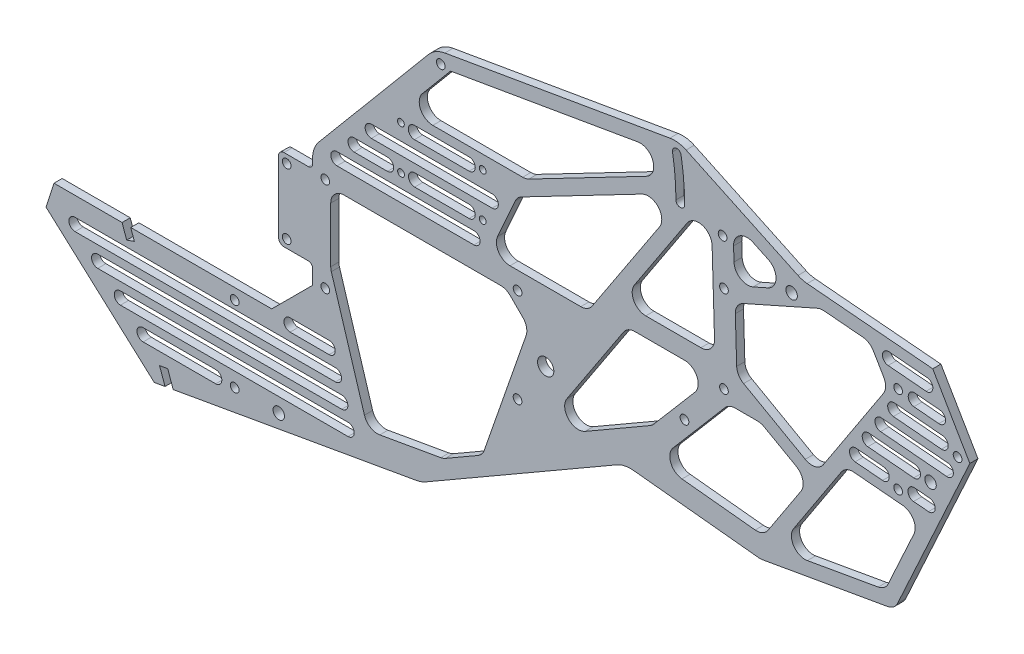
SolidWorks part; units mm, degrees
ref_plane "Front Plane" through (0, 0, 0) normal (0, 0, 1) x (1, 0, 0)
ref_plane "Top Plane" through (0, 0, 0) normal (0, 1, 0) x (1, 0, 0)
ref_plane "Right Plane" through (0, 0, 0) normal (1, 0, 0) x (0, 0, -1)
sketch "Sketch1" plane through (0, 0, 0) normal (0, 0, 1) x (1, 0, 0)
  line L0 (-2, -20.1357) -> (-28.6473, -20.1357) construction
  line L1 (-28.6473, -15.5958) -> (-2, -15.5958) construction
  line L2 (46.6267, -12.6057) -> (-36.9862, -12.6057) construction
  line L3 (-36.9862, -8.0658) -> (46.6267, -8.0658) construction
  line L4 (44.3092, -5.0757) -> (-45.3251, -5.0757) construction
  line L5 (-45.3251, -0.5358) -> (44.3092, -0.5358) construction
  line L6 (41.9917, 2.4543) -> (-53.664, 2.4543) construction
  line L7 (-53.664, 6.9942) -> (41.9917, 6.9942) construction
  line L8 (39.6742, 9.9843) -> (25.3518, 9.9843) construction
  line L9 (25.3518, 14.5242) -> (39.6742, 14.5242) construction
  line L10 (-2, -20.1357) -> (-28.6473, -20.1357)
  line L11 (-28.6473, -15.5958) -> (-2, -15.5958)
  line L12 (46.6267, -12.6057) -> (-36.9862, -12.6057)
  line L13 (-36.9862, -8.0658) -> (46.6267, -8.0658)
  line L14 (44.3092, -5.0757) -> (-45.3251, -5.0757)
  line L15 (-45.3251, -0.5358) -> (44.3092, -0.5358)
  line L16 (41.9917, 2.4543) -> (-53.664, 2.4543)
  line L17 (-53.664, 6.9942) -> (41.9917, 6.9942)
  line L18 (39.6742, 9.9843) -> (25.3518, 9.9843)
  line L19 (25.3518, 14.5242) -> (39.6742, 14.5242)
  line L20 (80.7464, -2.2866) -> (58.3209, -6.2408) construction
  line L21 (106.2441, 62.0298) -> (110.8759, 57.3979) construction
  line L22 (45.2764, 63.4942) -> (102.7085, 63.4942) construction
  line L23 (40.2764, 38.2462) -> (40.2764, 58.4942) construction
  line L24 (52.6739, -2.7875) -> (40.4976, 36.7755) construction
  line L25 (112.0626, 52.2191) -> (96.66, 7.9568) construction
  line L26 (33.6064, 69.3545) -> (33.6064, 67.4942)
  line L27 (76.2479, 123.8124) -> (35.946, 75.7824)
  line L28 (164.9022, 141.4902) -> (82.21, 127.2392)
  line L29 (211.9524, 121.3273) -> (170.8618, 140.6821)
  line L30 (261.4848, 116.375) -> (215.3421, 120.412)
  line L31 (275.1174, 93.0694) -> (261.4848, 116.375)
  line L32 (266.371, 74.0309) -> (275.1174, 93.0694)
  line L33 (151.4467, 29.0597) -> (212.4327, 22.7334)
  line L34 (75.0971, -12.8246) -> (145.4149, 27.7734)
  line L35 (-17.6047, -29.7828) -> (71.8336, -14.0124)
  line L36 (-19.6192, -24.1311) -> (-17.6047, -29.7828)
  line L37 (-22.6157, -24.6595) -> (-19.6192, -24.1311)
  line L38 (-20.6012, -30.3112) -> (-22.6157, -24.6595)
  line L39 (-24.5404, -31.0058) -> (-20.6012, -30.3112)
  line L40 (-64.3382, 4.9315) -> (-24.5404, -31.0058)
  line L41 (-61.3936, 13.9942) -> (-64.3382, 4.9315)
  line L42 (-36.3936, 13.9942) -> (-61.3936, 13.9942)
  line L43 (-34.6915, 9.2192) -> (-36.3936, 13.9942)
  line L44 (-31.8657, 10.2264) -> (-34.6915, 9.2192)
  line L45 (-33.2087, 13.9942) -> (-31.8657, 10.2264)
  line L46 (18.6064, 13.9942) -> (-33.2087, 13.9942)
  line L47 (33.6064, 28.9942) -> (18.6064, 13.9942)
  line L48 (33.6064, 34.4942) -> (33.6064, 28.9942)
  line L49 (23.1064, 35.9942) -> (32.1064, 35.9942)
  line L50 (21.1064, 63.9942) -> (21.1064, 37.9942)
  line L51 (32.1064, 65.9942) -> (23.1064, 65.9942)
  line L52 (33.6064, 69.3545) -> (33.6064, 67.4942)
  line L53 (76.2479, 123.8124) -> (35.946, 75.7824)
  line L54 (164.9022, 141.4902) -> (82.21, 127.2392)
  line L55 (211.9524, 121.3273) -> (170.8618, 140.6821)
  line L56 (261.4848, 116.375) -> (215.3421, 120.412)
  line L57 (275.1174, 93.0694) -> (261.4848, 116.375)
  line L58 (266.371, 74.0309) -> (275.1174, 93.0694)
  line L59 (151.4467, 29.0597) -> (212.4327, 22.7334)
  line L60 (75.0971, -12.8246) -> (145.4149, 27.7734)
  line L61 (-17.6047, -29.7828) -> (71.8336, -14.0124)
  line L62 (-19.6192, -24.1311) -> (-17.6047, -29.7828)
  line L63 (-22.6157, -24.6595) -> (-19.6192, -24.1311)
  line L64 (-20.6012, -30.3112) -> (-22.6157, -24.6595)
  line L65 (-24.5404, -31.0058) -> (-20.6012, -30.3112)
  line L66 (-64.3382, 4.9315) -> (-24.5404, -31.0058)
  line L67 (-61.3936, 13.9942) -> (-64.3382, 4.9315)
  line L68 (-36.3936, 13.9942) -> (-61.3936, 13.9942)
  line L69 (-34.6915, 9.2192) -> (-36.3936, 13.9942)
  line L70 (-31.8657, 10.2264) -> (-34.6915, 9.2192)
  line L71 (-33.2087, 13.9942) -> (-31.8657, 10.2264)
  line L72 (18.6064, 13.9942) -> (-33.2087, 13.9942)
  line L73 (33.6064, 28.9942) -> (18.6064, 13.9942)
  line L74 (33.6064, 34.4942) -> (33.6064, 28.9942)
  line L75 (23.1064, 35.9942) -> (32.1064, 35.9942)
  line L76 (21.1064, 63.9942) -> (21.1064, 37.9942)
  line L77 (32.1064, 65.9942) -> (23.1064, 65.9942)
  line L78 (94.4378, 5.2699) -> (82.3782, -1.6927) construction
  line L79 (112.0626, 52.2191) -> (96.66, 7.9568)
  line L80 (94.4378, 5.2699) -> (82.3782, -1.6927)
  line L81 (80.7464, -2.2866) -> (58.3209, -6.2408)
  line L82 (52.6739, -2.7875) -> (40.4976, 36.7755)
  line L83 (40.2764, 38.2462) -> (40.2764, 58.4942)
  line L84 (45.2764, 63.4942) -> (102.7085, 63.4942)
  line L85 (106.2441, 62.0298) -> (110.8759, 57.3979)
  arc A0 (46.6267, -12.6057) -> (46.6267, -8.0658) centre (46.6267, -10.3357) ccw construction
  arc A1 (44.3092, -5.0757) -> (44.3092, -0.5358) centre (44.3092, -2.8057) ccw construction
  circle A2 centre (5, -17.8657) radius 1.6 construction
  arc A3 (-2, -20.1357) -> (-2, -15.5958) centre (-2, -17.8657) ccw construction
  arc A4 (-28.6473, -15.5958) -> (-28.6473, -20.1357) centre (-28.6473, -17.8657) ccw construction
  arc A5 (-36.9862, -8.0658) -> (-36.9862, -12.6057) centre (-36.9862, -10.3357) ccw construction
  arc A6 (-45.3251, -0.5358) -> (-45.3251, -5.0757) centre (-45.3251, -2.8057) ccw construction
  arc A7 (-53.664, 6.9942) -> (-53.664, 2.4543) centre (-53.664, 4.7243) ccw construction
  arc A8 (41.9917, 2.4543) -> (41.9917, 6.9942) centre (41.9917, 4.7243) ccw construction
  arc A9 (39.6742, 9.9843) -> (39.6742, 14.5242) centre (39.6742, 12.2543) ccw construction
  arc A10 (25.3518, 14.5242) -> (25.3518, 9.9843) centre (25.3518, 12.2543) ccw construction
  circle A11 centre (5, 9.9942) radius 1.6 construction
  arc A12 (46.6267, -12.6057) -> (46.6267, -8.0658) centre (46.6267, -10.3357) ccw
  arc A13 (35.946, 75.7824) -> (33.6064, 69.3545) centre (43.6064, 69.3545) ccw
  arc A14 (82.21, 127.2392) -> (76.2479, 123.8124) centre (83.9084, 117.3845) ccw
  arc A15 (170.8618, 140.6821) -> (164.9022, 141.4902) centre (166.6006, 131.6355) ccw
  arc A16 (211.9524, 121.3273) -> (215.3421, 120.412) centre (216.2136, 130.3739) ccw
  arc A17 (266.371, 74.0309) -> (267.1092, 64.3518) centre (275.4579, 69.8563) ccw
  arc A18 (217.8289, 20.4471) -> (267.1092, 64.3518) centre (239.2664, 45.9942) ccw
  arc A19 (217.8289, 20.4471) -> (212.4327, 22.7334) centre (211.4009, 12.7868) ccw
  arc A20 (151.4467, 29.0597) -> (145.4149, 27.7734) centre (150.4149, 19.1131) ccw
  arc A21 (71.8336, -14.0124) -> (75.0971, -12.8246) centre (70.0971, -4.1643) ccw
  arc A22 (33.6064, 34.4942) -> (32.1064, 35.9942) centre (32.1064, 34.4942) ccw
  arc A23 (21.1064, 37.9942) -> (23.1064, 35.9942) centre (23.1064, 37.9942) ccw
  arc A24 (23.1064, 65.9942) -> (21.1064, 63.9942) centre (23.1064, 63.9942) ccw
  arc A25 (32.1064, 65.9942) -> (33.6064, 67.4942) centre (32.1064, 67.4942) ccw
  arc A26 (35.946, 75.7824) -> (33.6064, 69.3545) centre (43.6064, 69.3545) ccw
  arc A27 (82.21, 127.2392) -> (76.2479, 123.8124) centre (83.9084, 117.3845) ccw
  arc A28 (170.8618, 140.6821) -> (164.9022, 141.4902) centre (166.6006, 131.6355) ccw
  arc A29 (211.9524, 121.3273) -> (215.3421, 120.412) centre (216.2136, 130.3739) ccw
  arc A30 (266.371, 74.0309) -> (267.1092, 64.3518) centre (275.4579, 69.8563) ccw
  arc A31 (217.8289, 20.4471) -> (267.1092, 64.3518) centre (239.2664, 45.9942) ccw
  arc A32 (217.8289, 20.4471) -> (212.4327, 22.7334) centre (211.4009, 12.7868) ccw
  arc A33 (151.4467, 29.0597) -> (145.4149, 27.7734) centre (150.4149, 19.1131) ccw
  arc A34 (71.8336, -14.0124) -> (75.0971, -12.8246) centre (70.0971, -4.1643) ccw
  arc A35 (33.6064, 34.4942) -> (32.1064, 35.9942) centre (32.1064, 34.4942) ccw
  arc A36 (21.1064, 37.9942) -> (23.1064, 35.9942) centre (23.1064, 37.9942) ccw
  arc A37 (23.1064, 65.9942) -> (21.1064, 63.9942) centre (23.1064, 63.9942) ccw
  arc A38 (32.1064, 65.9942) -> (33.6064, 67.4942) centre (32.1064, 67.4942) ccw
  arc A39 (44.3092, -5.0757) -> (44.3092, -0.5358) centre (44.3092, -2.8057) ccw
  circle A40 centre (5, -17.8657) radius 1.6
  arc A41 (-2, -20.1357) -> (-2, -15.5958) centre (-2, -17.8657) ccw
  arc A42 (-28.6473, -15.5958) -> (-28.6473, -20.1357) centre (-28.6473, -17.8657) ccw
  arc A43 (-36.9862, -8.0658) -> (-36.9862, -12.6057) centre (-36.9862, -10.3357) ccw
  arc A44 (-45.3251, -0.5358) -> (-45.3251, -5.0757) centre (-45.3251, -2.8057) ccw
  arc A45 (-53.664, 6.9942) -> (-53.664, 2.4543) centre (-53.664, 4.7243) ccw
  arc A46 (41.9917, 2.4543) -> (41.9917, 6.9942) centre (41.9917, 4.7243) ccw
  arc A47 (39.6742, 9.9843) -> (39.6742, 14.5242) centre (39.6742, 12.2543) ccw
  arc A48 (25.3518, 14.5242) -> (25.3518, 9.9843) centre (25.3518, 12.2543) ccw
  circle A49 centre (5, 9.9942) radius 1.6
  circle A50 centre (24.1064, 38.9942) radius 1.6 construction
  circle A51 centre (38.2764, 30.3942) radius 1.6 construction
  circle A52 centre (24.1064, 38.9942) radius 1.6
  circle A53 centre (38.2764, 30.3942) radius 1.6
  circle A54 centre (24.1064, 62.9942) radius 1.6 construction
  circle A55 centre (38.2764, 64.9942) radius 1.6 construction
  circle A56 centre (24.1064, 62.9942) radius 1.6
  circle A57 centre (38.2764, 64.9942) radius 1.6
  arc A58 (167.1243, 122.9242) -> (170.3243, 122.9242) centre (168.7243, 122.9242) ccw construction
  arc A59 (169.0226, 138.1414) -> (165.8691, 137.5979) centre (167.4459, 137.8696) ccw construction
  arc A60 (170.3243, 122.9242) -> (169.0226, 138.1414) centre (80.7243, 122.9242) ccw construction
  arc A61 (167.1243, 122.9242) -> (165.8691, 137.5979) centre (80.7243, 122.9242) ccw construction
  circle A62 centre (80.7243, 122.9242) radius 1.6 construction
  arc A63 (167.1243, 122.9242) -> (170.3243, 122.9242) centre (168.7243, 122.9242) ccw
  arc A64 (169.0226, 138.1414) -> (165.8691, 137.5979) centre (167.4459, 137.8696) ccw
  arc A65 (170.3243, 122.9242) -> (169.0226, 138.1414) centre (80.7243, 122.9242) ccw
  arc A66 (167.1243, 122.9242) -> (165.8691, 137.5979) centre (80.7243, 122.9242) ccw
  circle A67 centre (80.7243, 122.9242) radius 1.6
  arc A68 (106.2441, 62.0298) -> (102.7085, 63.4942) centre (102.7085, 58.4942) ccw construction
  arc A69 (45.2764, 63.4942) -> (40.2764, 58.4942) centre (45.2764, 58.4942) ccw construction
  arc A70 (40.2764, 38.2462) -> (40.4976, 36.7755) centre (45.2764, 38.2462) ccw construction
  arc A71 (52.6739, -2.7875) -> (58.3209, -6.2408) centre (57.4527, -1.3168) ccw construction
  arc A72 (112.0626, 52.2191) -> (110.8759, 57.3979) centre (107.3404, 53.8624) ccw construction
  arc A73 (94.4378, 5.2699) -> (96.66, 7.9568) centre (91.9378, 9.6) ccw construction
  arc A74 (80.7464, -2.2866) -> (82.3782, -1.6927) centre (79.8782, 2.6375) ccw construction
  arc A75 (112.0626, 52.2191) -> (110.8759, 57.3979) centre (107.3404, 53.8624) ccw
  arc A76 (94.4378, 5.2699) -> (96.66, 7.9568) centre (91.9378, 9.6) ccw
  arc A77 (80.7464, -2.2866) -> (82.3782, -1.6927) centre (79.8782, 2.6375) ccw
  arc A78 (52.6739, -2.7875) -> (58.3209, -6.2408) centre (57.4527, -1.3168) ccw
  arc A79 (40.2764, 38.2462) -> (40.4976, 36.7755) centre (45.2764, 38.2462) ccw
  arc A80 (45.2764, 63.4942) -> (40.2764, 58.4942) centre (45.2764, 58.4942) ccw
  arc A81 (106.2441, 62.0298) -> (102.7085, 63.4942) centre (102.7085, 58.4942) ccw
  circle A82 centre (108.9365, 30.3942) radius 1.6 construction
  circle A83 centre (119.2664, 45.9942) radius 3 construction
  circle A84 centre (108.9365, 64.9942) radius 1.6 construction
  circle A85 centre (108.9365, 30.3942) radius 1.6
  circle A86 centre (119.2664, 45.9942) radius 3
  circle A87 centre (108.9365, 64.9942) radius 1.6
  circle A88 centre (21.1867, -17.8657) radius 2.1 construction
  circle A89 centre (21.1867, -17.8657) radius 2.1
  dimension "D1" = 0
extrude "Boss-Extrude1" add sketch "Sketch1" along normal blind 3
sketch "Sketch2" plane through (0, 0, 3) normal (0, 0, 1) x (1, 0, 0)
  line L0 (151.4467, 29.0597) -> (212.4327, 22.7334) construction
  line L1 (266.371, 74.0309) -> (275.1174, 93.0694) construction
  line L2 (151.4467, 29.0597) -> (241.4229, 19.7261)
  line L3 (241.4229, 19.7261) -> (275.1174, 93.0694)
  line L4 (275.1174, 93.0694) -> (318.5318, -44.2627)
  line L5 (318.5318, -44.2627) -> (151.4467, 29.0597)
extrude "Cut-Extrude1" cut sketch "Sketch2" against normal blind 3
sketch "Sketch3" plane through (0, 0, 3) normal (0, 0, 1) x (1, 0, 0)
  line L0 (198.2297, 24.2068) -> (247.4701, 32.8892)
  line L1 (151.4467, 29.0597) -> (241.4229, 19.7261) construction
  line L2 (241.4229, 19.7261) -> (275.1174, 93.0694) construction
  line L3 (247.4701, 32.8892) -> (241.4229, 19.7261)
  line L4 (241.4229, 19.7261) -> (198.2297, 24.2068)
  line L5 (-17.6047, -29.7828) -> (71.8336, -14.0124) construction
  dimension "D1" = 50
extrude "Cut-Extrude2" cut sketch "Sketch3" against normal blind 3
sketch "Sketch4" plane through (0, 0, 3) normal (0, 0, 1) x (1, 0, 0)
  circle A0 centre (184.7676, 103.569) radius 1.6
  circle A1 centre (184.7676, 71.569) radius 1.6
  circle A2 centre (248.7676, 103.569) radius 1.6
  circle A3 centre (248.7676, 71.569) radius 1.6
  circle A4 centre (66.0577, 96.9942) radius 1.25
  circle A5 centre (96.1205, 96.9942) radius 1.25
  circle A6 centre (66.1205, 80.9942) radius 1.25
  circle A7 centre (96.1205, 80.9942) radius 1.25
  dimension "D1" = 3.2
  dimension "D2" = 2.5
extrude "Cut-Extrude3" cut sketch "Sketch4" against normal blind 3
sketch "Sketch5" plane through (0, 0, 3) normal (0, 0, 1) x (1, 0, 0)
  line L0 (275.1174, 93.0694) -> (261.4848, 116.375) construction
  line L1 (247.4701, 32.8892) -> (275.1174, 93.0694) construction
  line L2 (261.4848, 116.375) -> (215.3421, 120.412) construction
  line L3 (261.4848, 116.375) -> (175.0201, 123.9397) construction
  line L4 (174.2676, 116.569) -> (174.2676, 58.569) construction
  line L5 (174.2676, 58.569) -> (259.2676, 58.569) construction
  circle A0 centre (184.2676, 120.1192) radius 1.6
  circle A1 centre (170.2676, 54.569) radius 1.6
  circle A2 centre (270.6134, 92.8471) radius 1.6
  circle A3 centre (209.6414, 114.6168) radius 2.1 construction
  circle A4 centre (260.6856, 79.8763) radius 2.1 construction
  circle A5 centre (209.6414, 114.6168) radius 2.1
  circle A6 centre (260.6856, 79.8763) radius 2.1
  dimension "D1" = 3.2
  dimension "D2" = 4
  dimension "D3" = 4
  dimension "D4" = 3
  dimension "D5" = 10
  dimension "D6" = 4
  dimension "D7" = 4
extrude "Cut-Extrude4" cut sketch "Sketch5" against normal blind 3
sketch "Sketch6" plane through (0, 0, 3) normal (0, 0, 1) x (1, 0, 0)
  line L0 (132.1655, 71.4942) -> (84.696, 71.4942) construction
  line L1 (161.0949, 111.3374) -> (136.3415, 73.7445) construction
  line L2 (82.3875, 80.9294) -> (154.6103, 118.5223) construction
  line L3 (156.2676, 125.0217) -> (54.5167, 72.0591) construction
  line L4 (48.3779, 79.7082) -> (83.6011, 121.6854) construction
  line L5 (85.3897, 122.7135) -> (153.1099, 134.3842) construction
  line L6 (134.8598, 71.4942) -> (98.4618, 71.4942)
  line L7 (161.0949, 111.3374) -> (134.8598, 71.4942)
  line L8 (108.7652, 94.6593) -> (154.6103, 118.5223)
  line L9 (156.2676, 125.0217) -> (112.0276, 101.9942)
  line L10 (67.0782, 101.9942) -> (84.3071, 122.5269)
  line L11 (84.3071, 122.5269) -> (153.1099, 134.3842)
  line L12 (67.0782, 101.9942) -> (112.0276, 101.9942)
  line L13 (108.7652, 94.6593) -> (98.4618, 71.4942)
  line L14 (42.5653, 73.7642) -> (92.9047, 73.7642) construction
  line L15 (42.5653, 76.0341) -> (92.9047, 76.0341)
  line L16 (42.5653, 71.4942) -> (92.9047, 71.4942)
  line L17 (48.8838, 81.2942) -> (61.1205, 81.2942) construction
  line L18 (48.8838, 83.5641) -> (61.1205, 83.5641)
  line L19 (48.8838, 79.0242) -> (61.1205, 79.0242)
  line L20 (71.1205, 81.2942) -> (91.1205, 81.2942) construction
  line L21 (71.1205, 83.5641) -> (91.1205, 83.5641)
  line L22 (71.1205, 79.0242) -> (91.1205, 79.0242)
  line L23 (55.2022, 88.8242) -> (99.6031, 88.8242) construction
  line L24 (55.2022, 91.0941) -> (99.6031, 91.0941)
  line L25 (55.2022, 86.5542) -> (99.6031, 86.5542)
  line L26 (71.0577, 96.3542) -> (91.1205, 96.3542) construction
  line L27 (71.0577, 98.6241) -> (91.1205, 98.6241)
  line L28 (71.0577, 94.0842) -> (91.1205, 94.0842)
  line L29 (42.5653, 73.7642) -> (55.2022, 88.8242) construction
  line L30 (76.2479, 123.8124) -> (35.946, 75.7824) construction
  line L31 (92.9047, 73.7642) -> (99.6031, 88.8242) construction
  arc A0 (42.5653, 76.0341) -> (42.5653, 71.4942) centre (42.5653, 73.7642) ccw
  arc A1 (92.9047, 71.4942) -> (92.9047, 76.0341) centre (92.9047, 73.7642) ccw
  arc A2 (39.6742, 9.9843) -> (39.6742, 14.5242) centre (39.6742, 12.2543) ccw construction
  arc A3 (48.8838, 83.5641) -> (48.8838, 79.0242) centre (48.8838, 81.2942) ccw
  arc A4 (61.1205, 79.0242) -> (61.1205, 83.5641) centre (61.1205, 81.2942) ccw
  arc A5 (71.1205, 83.5641) -> (71.1205, 79.0242) centre (71.1205, 81.2942) ccw
  arc A6 (91.1205, 79.0242) -> (91.1205, 83.5641) centre (91.1205, 81.2942) ccw
  arc A7 (55.2022, 91.0941) -> (55.2022, 86.5542) centre (55.2022, 88.8242) ccw
  arc A8 (99.6031, 86.5542) -> (99.6031, 91.0941) centre (99.6031, 88.8242) ccw
  arc A9 (71.0577, 98.6241) -> (71.0577, 94.0842) centre (71.0577, 96.3542) ccw
  arc A10 (91.1205, 94.0842) -> (91.1205, 98.6241) centre (91.1205, 96.3542) ccw
  circle A11 centre (66.1205, 80.9942) radius 1.25 construction
  circle A12 centre (96.1205, 80.9942) radius 1.25 construction
  circle A13 centre (96.1205, 96.9942) radius 1.25 construction
  circle A14 centre (66.0577, 96.9942) radius 1.25 construction
  arc A15 (161.0949, 111.3374) -> (154.6103, 118.5223) centre (156.9189, 114.0871) ccw
  arc A16 (156.2676, 125.0217) -> (153.1099, 134.3842) centre (153.9591, 129.4569) ccw
  point P11 (67.735, 73.7642)
  point P32 (55.0021, 81.2942)
  point P37 (81.1205, 81.2942)
  point P44 (77.4026, 88.8242)
  point P53 (81.0891, 96.3542)
  point P72 (96.1205, 80.9942)
  dimension "D9" = 5
  dimension "D10" = 6
  dimension "D11" = 5
  dimension "D1" = 7.53
  dimension "D2" = 7.53
  dimension "D3" = 7.53
  dimension "D4" = 5
  dimension "D5" = 5
  dimension "D6" = 5
  dimension "D7" = 5
  dimension "D8" = 5
extrude "Cut-Extrude5" cut sketch "Sketch6" against normal blind 3
sketch "Sketch7" plane through (0, 0, 3) normal (0, 0, 1) x (1, 0, 0)
  line L0 (159.965, 100.5296) -> (177.5624, 127.2548) construction
  line L1 (146.7725, 80.4942) -> (179.9411, 130.8673)
  line L2 (183.869, 129.0284) -> (201.5125, 120.7179) construction
  line L3 (188.0599, 127.0544) -> (201.0419, 120.9395)
  line L4 (149.3472, 73.4942) -> (181.1523, 73.4942)
  line L5 (181.1523, 73.4942) -> (158.3971, 46.8156)
  line L6 (158.3971, 46.8156) -> (115.4559, 22.0236)
  line L7 (115.4559, 22.0236) -> (149.3472, 73.4942)
  line L8 (134.8598, 71.4942) -> (161.0949, 111.3374) construction
  line L9 (75.0971, -12.8246) -> (145.4149, 27.7734) construction
  line L10 (179.9411, 130.8673) -> (181.4629, 80.4942)
  line L11 (181.4629, 80.4942) -> (146.7725, 80.4942)
  line L12 (186.6132, 67.569) -> (159.881, 36.2278)
  line L13 (159.881, 36.2278) -> (199.2731, 32.1414)
  line L14 (199.2731, 32.1414) -> (215.9786, 57.6554)
  line L15 (215.9786, 57.6554) -> (198.4056, 67.569)
  line L16 (186.6132, 67.569) -> (198.4056, 67.569)
  line L17 (188.8469, 101.004) -> (189.5324, 78.3155)
  line L18 (189.5324, 78.3155) -> (218.7235, 61.8477)
  line L19 (218.7235, 61.8477) -> (245.0335, 102.0304)
  line L20 (245.0335, 102.0304) -> (238.397, 113.3758)
  line L21 (238.397, 113.3758) -> (220.2717, 114.9616)
  line L22 (220.2717, 114.9616) -> (188.8469, 101.004)
  line L23 (200.9409, 111.8467) -> (188.6838, 106.4026)
  line L24 (188.6838, 106.4026) -> (188.0599, 127.0544)
  line L25 (229.5376, 69.2361) -> (204.0505, 30.3103)
  line L26 (204.0505, 30.3103) -> (244.0207, 37.3581)
  line L27 (244.0207, 37.3581) -> (257.5403, 66.7862)
  line L28 (257.5403, 66.7862) -> (229.5376, 69.2361)
  line L29 (247.4701, 32.8892) -> (198.2297, 24.2068) construction
  line L30 (247.4701, 32.8892) -> (275.1174, 93.0694) construction
  line L31 (151.4467, 29.0597) -> (198.2297, 24.2068) construction
  line L32 (98.4618, 71.4942) -> (134.8598, 71.4942) construction
  line L34 (261.4848, 116.375) -> (215.3421, 120.412) construction
  line L35 (275.1174, 93.0694) -> (261.4848, 116.375) construction
  line L36 (245.288, 111.4982) -> (259.2599, 110.2758) construction
  line L37 (245.4858, 113.7595) -> (259.4578, 112.5371)
  line L38 (245.0901, 109.2369) -> (259.0621, 108.0145)
  line L39 (254.7501, 103.1116) -> (263.9199, 102.3093) construction
  line L40 (254.948, 105.3729) -> (264.1177, 104.5706)
  line L41 (254.5523, 100.8503) -> (263.7221, 100.048)
  line L42 (247.2011, 96.2133) -> (264.8954, 94.6652) construction
  line L43 (247.399, 98.4746) -> (265.0933, 96.9265)
  line L44 (247.0033, 93.9519) -> (264.6976, 92.4039)
  line L45 (242.5201, 89.064) -> (266.799, 86.9399) construction
  line L46 (242.718, 91.3253) -> (266.9969, 89.2012)
  line L47 (242.3223, 86.8027) -> (266.6012, 84.6786)
  line L48 (237.8391, 81.9148) -> (254.712, 80.4386) construction
  line L49 (238.0369, 84.1761) -> (254.9098, 82.6999)
  line L50 (237.6413, 79.6535) -> (254.5142, 78.1773)
  line L51 (233.1581, 74.7656) -> (243.2323, 73.8842) construction
  line L52 (233.3559, 77.0269) -> (243.4301, 76.1455)
  line L53 (232.9602, 72.5043) -> (243.0344, 71.6229)
  line L54 (254.6209, 72.8878) -> (260.1223, 72.4065) construction
  line L55 (254.8187, 75.1491) -> (260.3201, 74.6678)
  line L56 (254.423, 70.6265) -> (259.9244, 70.1452)
  circle A0 centre (119.2664, 45.9942) radius 3 construction
  circle A1 centre (184.2676, 120.1192) radius 1.6 construction
  circle A2 centre (184.7676, 103.569) radius 1.6 construction
  circle A3 centre (209.6414, 114.6168) radius 2.1 construction
  circle A4 centre (170.2676, 54.569) radius 1.6 construction
  circle A5 centre (184.7676, 71.569) radius 1.6 construction
  circle A6 centre (248.7676, 103.569) radius 1.6 construction
  circle A7 centre (248.7676, 71.569) radius 1.6 construction
  arc A8 (245.4858, 113.7595) -> (245.0901, 109.2369) centre (245.288, 111.4982) ccw
  arc A9 (259.0621, 108.0145) -> (259.4578, 112.5371) centre (259.2599, 110.2758) ccw
  arc A10 (254.948, 105.3729) -> (254.5523, 100.8503) centre (254.7501, 103.1116) ccw
  arc A11 (263.7221, 100.048) -> (264.1177, 104.5706) centre (263.9199, 102.3093) ccw
  arc A12 (247.399, 98.4746) -> (247.0033, 93.9519) centre (247.2011, 96.2133) ccw
  arc A13 (264.6976, 92.4039) -> (265.0933, 96.9265) centre (264.8954, 94.6652) ccw
  arc A14 (242.718, 91.3253) -> (242.3223, 86.8027) centre (242.5201, 89.064) ccw
  arc A15 (266.6012, 84.6786) -> (266.9969, 89.2012) centre (266.799, 86.9399) ccw
  arc A16 (238.0369, 84.1761) -> (237.6413, 79.6535) centre (237.8391, 81.9148) ccw
  arc A17 (254.5142, 78.1773) -> (254.9098, 82.6999) centre (254.712, 80.4386) ccw
  arc A18 (233.3559, 77.0269) -> (232.9602, 72.5043) centre (233.1581, 74.7656) ccw
  arc A19 (243.0344, 71.6229) -> (243.4301, 76.1455) centre (243.2323, 73.8842) ccw
  arc A20 (254.8187, 75.1491) -> (254.423, 70.6265) centre (254.6209, 72.8878) ccw
  arc A21 (259.9244, 70.1452) -> (260.3201, 74.6678) centre (260.1223, 72.4065) ccw
  arc A22 (46.6267, -12.6057) -> (46.6267, -8.0658) centre (46.6267, -10.3357) ccw construction
  circle A23 centre (270.6134, 92.8471) radius 1.6 construction
  circle A24 centre (260.6856, 79.8763) radius 2.1 construction
  arc A25 (201.0419, 120.9395) -> (200.9409, 111.8467) centre (198.9113, 116.4162) cw
  point P39 (252.2739, 110.887)
  point P45 (259.335, 102.7104)
  point P67 (256.0483, 95.4392)
  point P82 (254.6596, 88.002)
  point P89 (246.2756, 81.1767)
  point P96 (238.1952, 74.3249)
  point P103 (257.3716, 72.6472)
  dimension "D2" = 10
  dimension "D7" = 4
  dimension "D11" = 1
  dimension "D14" = 4
  dimension "D29" = 4
  dimension "D35" = 6
  dimension "D36" = 6
  dimension "D37" = 6
  dimension "D40" = 5
  dimension "D41" = 5
  dimension "D42" = 5
  dimension "D43" = 5
  dimension "D44" = 5
  dimension "D1" = 10
  dimension "D3" = 8
  dimension "D4" = 5
  dimension "D5" = 5
  dimension "D6" = 4
  dimension "D8" = 4
  dimension "D9" = 4
  dimension "D10" = 4
  dimension "D12" = 7
  dimension "D13" = 4
  dimension "D15" = 4
  dimension "D16" = 4
  dimension "D17" = 2
  dimension "D18" = 4
  dimension "D19" = 5
  dimension "D20" = 4
  dimension "D21" = 5
  dimension "D22" = 5
  dimension "D23" = 4
  dimension "D24" = 7.53
  dimension "D25" = 7.53
  dimension "D26" = 7.53
  dimension "D27" = 7.53
  dimension "D28" = 7.53
  dimension "D30" = 5
  dimension "D31" = 5
  dimension "D32" = 6
  dimension "D33" = 5
  dimension "D34" = 5
  dimension "D38" = 5
  dimension "D39" = 6
extrude "Cut-Extrude6" cut sketch "Sketch7" against normal blind 3
fillet "Fillet1" radius 5 29 edges at (204.0505, 30.3103, 1.5) (186.6132, 67.569, 1.5) (198.4056, 67.569, 1.5) (229.5376, 69.2361, 1.5) (199.2731, 32.1414, 1.5) (244.0207, 37.3581, 1.5) (218.7235, 61.8477, 1.5) (257.5403, 66.7862, 1.5) (245.0335, 102.0304, 1.5) (238.397, 113.3758, 1.5) (188.8469, 101.004, 1.5) (220.2717, 114.9616, 1.5) (189.5324, 78.3155, 1.5) (159.881, 36.2278, 1.5) (115.4559, 22.0236, 1.5) (158.3971, 46.8156, 1.5) (181.1523, 73.4942, 1.5) (149.3472, 73.4942, 1.5) (188.6838, 106.4026, 1.5) (188.0599, 127.0544, 1.5) (181.4629, 80.4942, 1.5) (179.9411, 130.8673, 1.5) (146.7725, 80.4942, 1.5) (134.8598, 71.4942, 1.5) (98.4618, 71.4942, 1.5) (108.7652, 94.6593, 1.5) (67.0782, 101.9942, 1.5) (215.9786, 57.6554, 1.5) (112.0276, 101.9942, 1.5)
fillet "Fillet2" radius 5 2 edges at (198.2297, 24.2068, 1.5) (247.4701, 32.8892, 1.5)
